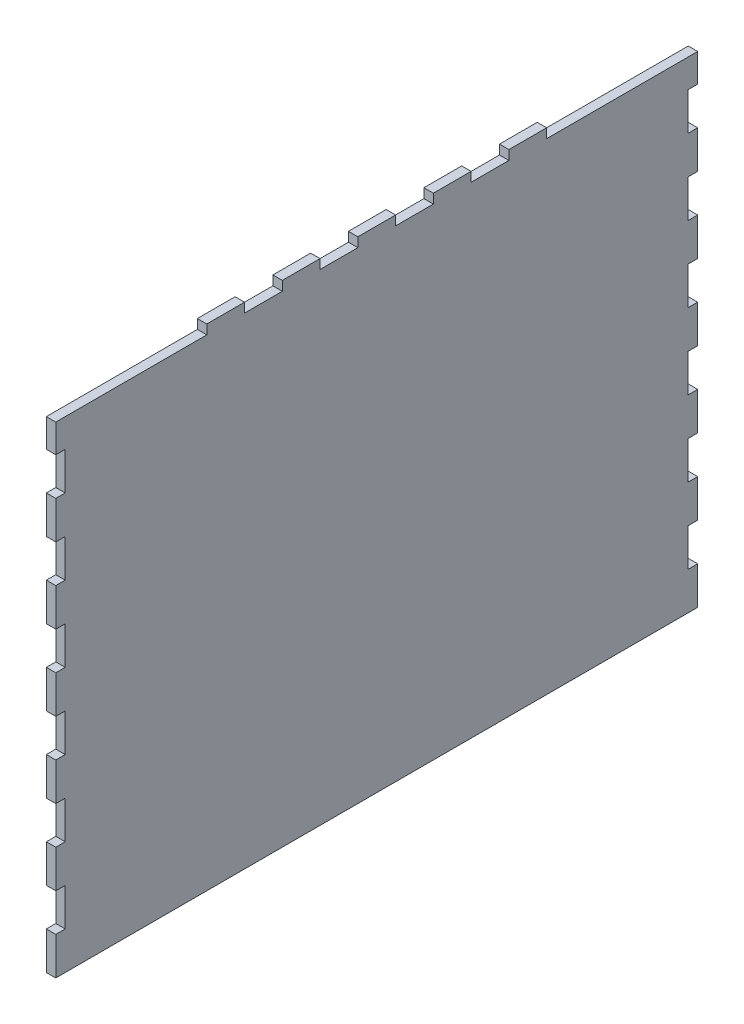
SolidWorks part; units mm, degrees
ref_plane "Front Plane" through (0, 0, 0) normal (0, 0, 1) x (1, 0, 0)
ref_plane "Top Plane" through (0, 0, 0) normal (0, 1, 0) x (1, 0, 0)
ref_plane "Right Plane" through (0, 0, 0) normal (1, 0, 0) x (0, 0, -1)
sketch "Sketch1" plane through (0, 0, 0) normal (1, 0, 0) x (0, 0, -1)
  line L5 (-107.95, 69.85) -> (-104.775, 69.85)
  line L6 (-107.95, -82.55) -> (107.95, -82.55)
  line L30 (-107.95, 82.55) -> (107.95, 82.55)
  line L32 (-107.95, -82.55) -> (107.95, 82.55) construction
  line L33 (-107.95, 82.55) -> (107.95, -82.55) construction
  line L34 (-104.775, 69.85) -> (-104.775, 57.15)
  line L35 (-104.775, 57.15) -> (-107.95, 57.15)
  line L36 (-107.95, 69.85) -> (-107.95, 82.55)
  line L37 (-107.95, 44.45) -> (-104.775, 44.45)
  line L38 (-104.775, 44.45) -> (-104.775, 31.75)
  line L39 (-104.775, 31.75) -> (-107.95, 31.75)
  line L40 (-107.95, 19.05) -> (-104.775, 19.05)
  line L41 (-104.775, 19.05) -> (-104.775, 6.35)
  line L42 (-104.775, 6.35) -> (-107.95, 6.35)
  line L43 (-107.95, -82.55) -> (-107.95, -69.85)
  line L44 (-107.95, -6.35) -> (-104.775, -6.35)
  line L45 (-104.775, -6.35) -> (-104.775, -19.05)
  line L46 (-104.775, -19.05) -> (-107.95, -19.05)
  line L47 (-107.95, -57.15) -> (-107.95, -44.45)
  line L48 (-107.95, -31.75) -> (-104.775, -31.75)
  line L49 (-104.775, -31.75) -> (-104.775, -44.45)
  line L50 (-104.775, -44.45) -> (-107.95, -44.45)
  line L51 (-107.95, -31.75) -> (-107.95, -19.05)
  line L52 (-107.95, -57.15) -> (-104.775, -57.15)
  line L53 (-104.775, -57.15) -> (-104.775, -69.85)
  line L54 (-104.775, -69.85) -> (-107.95, -69.85)
  line L56 (-107.95, -6.35) -> (-107.95, 6.35)
  line L57 (-107.95, 19.05) -> (-107.95, 31.75)
  line L58 (-107.95, 44.45) -> (-107.95, 57.15)
  line L59 (0, 82.55) -> (0, -82.55) construction
  line L60 (107.95, 44.45) -> (107.95, 57.15)
  line L61 (107.95, 19.05) -> (107.95, 31.75)
  line L62 (107.95, -6.35) -> (107.95, 6.35)
  line L63 (104.775, -69.85) -> (107.95, -69.85)
  line L64 (104.775, -57.15) -> (104.775, -69.85)
  line L65 (107.95, -57.15) -> (104.775, -57.15)
  line L66 (107.95, -31.75) -> (107.95, -19.05)
  line L67 (104.775, -44.45) -> (107.95, -44.45)
  line L68 (104.775, -31.75) -> (104.775, -44.45)
  line L69 (107.95, -31.75) -> (104.775, -31.75)
  line L70 (107.95, -57.15) -> (107.95, -44.45)
  line L71 (104.775, -19.05) -> (107.95, -19.05)
  line L72 (104.775, -6.35) -> (104.775, -19.05)
  line L73 (107.95, -6.35) -> (104.775, -6.35)
  line L74 (107.95, -82.55) -> (107.95, -69.85)
  line L75 (104.775, 6.35) -> (107.95, 6.35)
  line L76 (104.775, 19.05) -> (104.775, 6.35)
  line L77 (107.95, 19.05) -> (104.775, 19.05)
  line L78 (104.775, 31.75) -> (107.95, 31.75)
  line L79 (104.775, 44.45) -> (104.775, 31.75)
  line L80 (107.95, 44.45) -> (104.775, 44.45)
  line L81 (107.95, 69.85) -> (107.95, 82.55)
  line L82 (104.775, 57.15) -> (107.95, 57.15)
  line L83 (104.775, 69.85) -> (104.775, 57.15)
  line L84 (107.95, 69.85) -> (104.775, 69.85)
  point P0 (0, 0)
  dimension "D1" = 215.9
  dimension "D2" = 165.1
  dimension "D3" = 12.7
  dimension "D4" = 3.175
  dimension "D5" = 12.7
extrude "Boss-Extrude1" add sketch "Sketch1" along normal mid plane 3.175
sketch "Sketch2" plane through (0, 82.55, 0) normal (0, 1, 0) x (1, 0, 0)
  line L0 (-1.5875, -19.05) -> (1.5875, -19.05)
  line L1 (-1.5875, 107.95) -> (-1.5875, -107.95) construction
  line L2 (-1.5875, -19.05) -> (1.5875, -19.05) construction
  line L3 (1.5875, 107.95) -> (1.5875, -107.95) construction
  line L4 (-1.5875, -19.05) -> (-1.5875, -31.75)
  line L5 (1.5875, -31.75) -> (-1.5875, -31.75) construction
  line L6 (-1.5875, -31.75) -> (1.5875, -31.75)
  line L7 (1.5875, -31.75) -> (1.5875, -44.45)
  line L8 (-1.5875, -44.45) -> (1.5875, -44.45) construction
  line L9 (1.5875, -44.45) -> (-1.5875, -44.45)
  line L10 (-1.5875, -44.45) -> (-1.5875, -57.15)
  line L11 (1.5875, -57.15) -> (-1.5875, -57.15) construction
  line L12 (-1.5875, -57.15) -> (1.5875, -57.15)
  line L13 (1.5875, -57.15) -> (1.5875, -107.95)
  line L14 (1.5875, -107.95) -> (-5.7732, -107.95)
  line L15 (-5.7732, -107.95) -> (-5.7732, 107.95)
  line L16 (-1.5875, 107.95) -> (-153.9875, 107.95) construction
  line L17 (-5.7732, 107.95) -> (1.5875, 107.95)
  line L18 (1.5875, 107.95) -> (1.5875, 57.41)
  line L19 (1.5875, 57.15) -> (-1.5875, 57.15)
  line L20 (-1.5875, 57.15) -> (-1.5875, 44.45)
  line L21 (1.5875, -19.05) -> (1.5875, -6.35)
  line L22 (1.5875, 44.45) -> (-1.5875, 44.45)
  line L23 (1.5875, 44.45) -> (-1.5875, 44.45) construction
  line L24 (-1.5875, 57.15) -> (1.5875, 57.15) construction
  line L25 (1.5875, 31.75) -> (-1.5875, 31.75)
  line L27 (1.5875, 19.05) -> (-1.5875, 19.05)
  line L28 (1.5875, 19.05) -> (-1.5875, 19.05) construction
  line L29 (1.5875, 6.35) -> (-1.5875, 6.35)
  line L30 (-1.5875, 6.35) -> (1.5875, 6.35) construction
  line L31 (1.5875, -6.35) -> (-1.5875, -6.35)
  line L32 (1.5875, -6.35) -> (-1.5875, -6.35) construction
  line L33 (1.5875, 6.35) -> (1.5875, 19.05)
  line L34 (-1.5875, 6.35) -> (-1.5875, -6.35)
  line L35 (1.5875, 31.75) -> (1.5875, 44.45)
  line L36 (1.5875, 57.15) -> (1.5875, 57.41)
  line L37 (-1.5875, 31.75) -> (-1.5875, 19.05)
  point P8 (0, 0)
  point P40 (1.5875, 44.45)
  point P41 (1.5875, 57.15)
  point P54 (0, 0)
  point P55 (0, 0)
  point P56 (1.5875, 19.05)
  point P57 (2.2043, 31.75)
extrude "Cut-Extrude1" cut sketch "Sketch2" against normal blind 3.175
